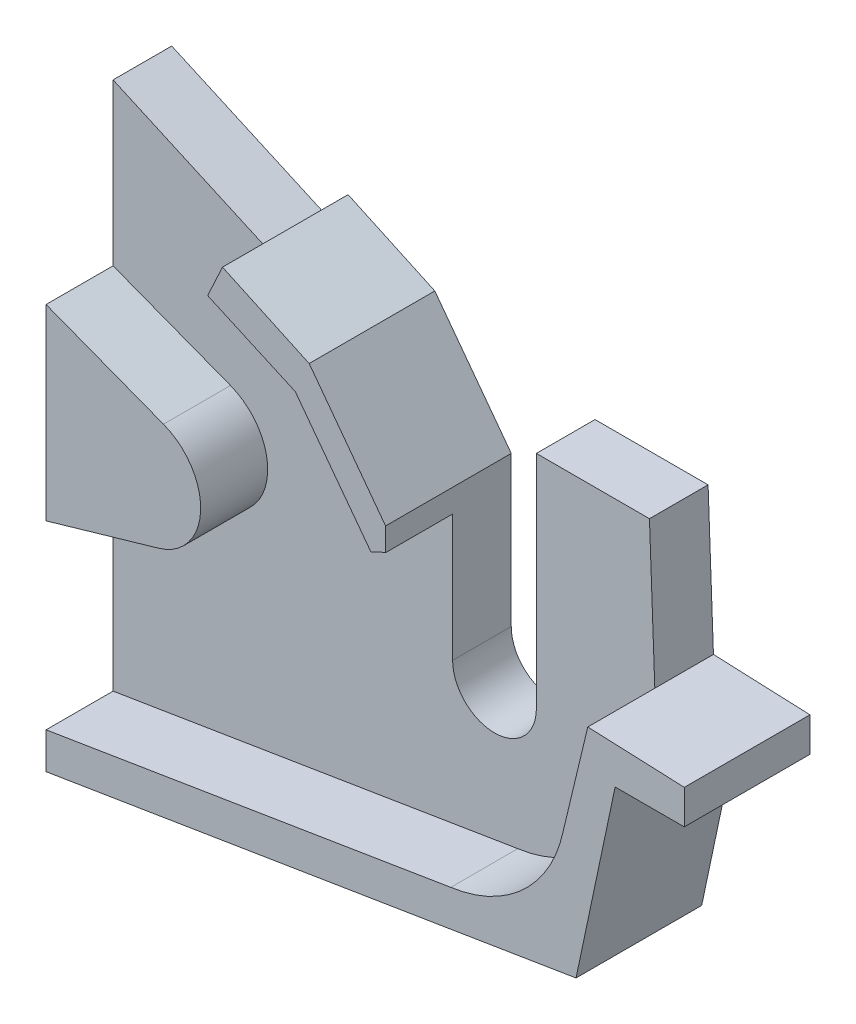
SolidWorks part; units mm, degrees
ref_plane "Front Plane" through (0, 0, 0) normal (0, 0, 1) x (1, 0, 0)
ref_plane "Top Plane" through (0, 0, 0) normal (0, 1, 0) x (1, 0, 0)
ref_plane "Right Plane" through (0, 0, 0) normal (1, 0, 0) x (0, 0, -1)
sketch "Sketch1" plane through (0, 0, 0) normal (0, 0, 1) x (1, 0, 0)
  line L0 (-48.8998, -64.1664) -> (-34.4801, 53.9567) construction
  line L3 (0, 51.4823) -> (78.4652, 51.4823)
  line L4 (78.4652, 0) -> (78.4652, 51.4823)
  line L5 (-0.9138, 14.6546) -> (9.0862, 14.6546)
  line L6 (9.0862, 14.6546) -> (9.0862, -2.3454)
  line L7 (9.0862, -2.3454) -> (-0.9138, -2.3454)
  line L8 (-0.9138, -2.3454) -> (-0.9138, 14.6546)
  line L9 (-0.9138, 14.6546) -> (-11.6983, 29.052)
  line L10 (-53.7784, 47.9405) -> (-11.6983, 29.052)
  line L11 (9.0862, 14.6546) -> (9.0862, 29.052)
  line L12 (9.0862, 29.052) -> (22.5862, 29.052)
  line L13 (-62.6952, 31.3187) -> (-27.4305, 17.8134)
  line L14 (-27.4305, 17.8134) -> (-29.904, 11.3546)
  line L15 (-29.904, 11.3546) -> (-32.3775, 4.8959)
  line L16 (-71.761, -7.9825) -> (-27.9913, 4.7082)
  line L17 (-41.4462, 23.181) -> (-41.4462, 0.807)
  line L18 (-27.9913, 4.7082) -> (-29.904, 11.3546)
  line L19 (-29.904, 11.3546) -> (-31.8166, 18.0011)
  line L20 (-74.7301, -26.2138) -> (-1.4754, -14.2813)
  line L21 (-1.4754, -14.2813) -> (7.6299, -12.7982)
  line L22 (23.2246, 11.8381) -> (20.0693, -1.3098)
  line L23 (23.2246, 11.8381) -> (34.7443, 11.3546)
  line L24 (-0.9138, 14.6546) -> (-0.9138, 20.5505)
  line L25 (-0.9138, 20.5505) -> (-7.2539, 29.052)
  line L26 (-7.2539, 29.052) -> (-10.0368, 32.7838)
  line L27 (-10.0368, 32.7838) -> (-20.3866, 37.57)
  line L28 (-20.3866, 37.57) -> (-22.1551, 33.7457)
  line L29 (-70.8332, -25.579) -> (-70.1459, -29.7983)
  line L30 (-70.1459, -29.7983) -> (21.8227, -14.8175)
  line L31 (21.8227, -14.8175) -> (26.4898, 7.2668)
  line L32 (26.4898, 7.2668) -> (34.7443, 7.2668)
  line L33 (34.7443, 7.2668) -> (34.7443, 11.3546)
  line L34 (-62.6952, 31.3187) -> (-53.7784, 47.9405)
  line L35 (-70.8332, -25.579) -> (-71.761, -7.9825)
  line L36 (22.5862, 29.052) -> (23.2246, 11.8381)
  line L37 (-41.4462, 0.807) -> (-41.4462, -25.1234)
  line L38 (-41.4462, 23.181) -> (-41.4462, 42.4049)
  circle A0 centre (4.0862, 2.6546) radius 5
  circle A1 centre (4.0862, 9.6546) radius 5
  circle A2 centre (-29.904, 11.3546) radius 6.9162
  circle A3 centre (4.6878, 2.8662) radius 15.9383
  dimension "D4" = 13.5
  dimension "D1" = 119
  dimension "D2" = 10
  dimension "D3" = 17
extrude "Boss-Extrude2" add sketch "Sketch1" along normal blind 7 contours L0 L37 L20 L21 A3 L9 L10 L13 A2 L16 | L13 L0 L10 L38 | L0 L16 A2 L13 | L16 L0 L13 L17 | L19 A2 L15 | L14 A2 L19 | L15 A2 L18 | L18 A2 L14 | A3 L21 L20 L37 L30 L31 L32 L33 L23 L22 | L9 A3 L21 L22 L11 L6 L7 L8 | A3 L22 L36 L12 L11 | A3 L24 L25 L26 L27 L28 L10 L9 | L37 L0 L16 | L21 A3 | L22 A3 | L24 A3 L9 | A0 L8 L7 | A0 L7 L6 region at (-40.5994, -22.9578, 0) region at (-41.2811, -0.4501, 0) region at (-22.9896, 6.2988, 0) region at (-40.4031, 14.3836, 0) region at (-39.4172, 11.4485, 0) region at (-39.3188, 32.736, 0) region at (-30.0977, 6.8278, 0) region at (-26.4032, 11.2048, 0) region at (-10.0718, -1.8401, 0) region at (7.2498, -12.862, 0) region at (-29.7102, 15.8815, 0) region at (-33.4048, 11.5045, 0) region at (-1.5042, 16.4942, 0) region at (-10.6922, 28.5754, 0) region at (20.182, -0.8522, 0) region at (17.0404, 20.1785, 0) region at (0.203, -1.2285, 0) region at (7.9693, -1.2285, 0)
extrude "Boss-Extrude3" add sketch "Sketch1<7>" along normal blind 15 contours L0 L16 A2 L13 | L19 A2 L15 | L16 L0 L13 L17 | L18 A2 L14 | L15 A2 L18 | L14 A2 L19 | A3 L24 L25 L26 L27 L28 L10 L9 | A3 L21 L20 L37 L30 L31 L32 L33 L23 L22 region at (-40.5994, -22.9578, 0) region at (-40.4031, 14.3836, 0) region at (-39.4172, 11.4485, 0) region at (-30.0977, 6.8278, 0) region at (-26.4032, 11.2048, 0) region at (-29.7102, 15.8815, 0) region at (-33.4048, 11.5045, 0) region at (-10.6922, 28.5754, 0)
sketch "Sketch1<7>" plane through (0, 0, 0) normal (0, 0, 1) x (1, 0, 0) same geometry as "Sketch1"
